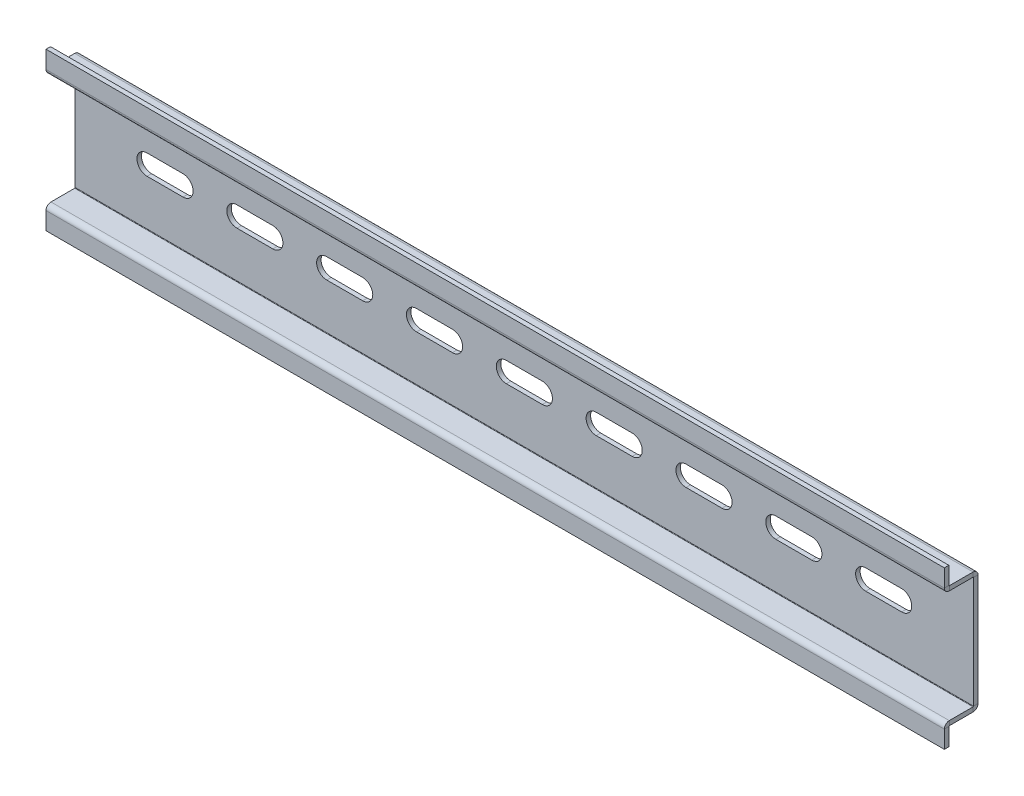
SolidWorks part; units mm, degrees
note: The reader was unsure of these and kept them because the rebuilt part matched: flange length of "边线-法兰1", "边线-法兰2".
material "冷轧钢板"
ref_plane "前视基准面" through (0, 0, 0) normal (0, 0, 1) x (1, 0, 0)
ref_plane "上视基准面" through (0, 0, 0) normal (0, 1, 0) x (1, 0, 0)
ref_plane "右视基准面" through (0, 0, 0) normal (1, 0, 0) x (0, 0, -1)
sketch "草图1" plane through (0, 0, 0) normal (0, 0, 1) x (1, 0, 0)
  line L1 (-100, 13.5) -> (100, 13.5)
  line L2 (-100, 13.5) -> (-100, -13.5)
  line L3 (-100, -13.5) -> (100, -13.5)
  line L4 (100, 13.5) -> (100, -13.5)
  line L5 (-100, 13.5) -> (100, -13.5) construction
  line L6 (-100, -13.5) -> (100, 13.5) construction
  point P0 (0, 0)
  dimension "D1" = 200
  dimension "D2" = 27
base flange "基体-法兰1" sketch "草图1" thickness 1 reverse thickness direction no parameters "D1"=0.1
edge flange "边线-法兰1" sketch "草图10" flange profiles "草图10", "草图11" flange angle 90 flange length 7.5 flange position material inside bend radius 0.1 thickness 1 parameters "D1"=1.5, "D6"=10, "D8"=1
sketch "草图10" plane through (0, 13.5, 0) normal (0, -1, 0) x (1, 0, 0)
  line L1 (100, 0) -> (-100, 0) construction
  line L2 (-100, 0) -> (-100, 6.5)
  line L3 (-100, 6.5) -> (100, 6.5)
  line L4 (100, 6.5) -> (100, 0)
  line L5 (100, 0) -> (-100, 0)
sketch "草图11" plane through (0, -13.5, 0) normal (0, 1, 0) x (-1, 0, 0)
  line L0 (100, 0) -> (-100, 0) construction
  line L1 (100, 0) -> (-100, 0)
  line L2 (100, 0) -> (100, 6.5)
  line L3 (100, 6.5) -> (-100, 6.5)
  line L4 (-100, 6.5) -> (-100, 0)
bend "边线折弯1" bend radius 0.1 bend angle 90 parameters "D5"=1
bend "边线折弯2" bend radius 0.1 bend angle 90 parameters "D5"=2
edge flange "边线-法兰2" sketch "草图16" flange profiles "草图16", "草图17" flange angle 90 flange length 5 flange position material inside bend radius 0.1 thickness 1 parameters "D1"=1.5, "D6"=10, "D8"=1
sketch "草图16" plane through (0, 13.5, 6.5) normal (0, 0, 1) x (1, 0, 0)
  line L2 (-100, 0) -> (-100, 4)
  line L3 (-100, 4) -> (100, 4)
  line L4 (100, 4) -> (100, 0)
  line L5 (100, 0) -> (-100, 0) construction
  line L6 (100, 0) -> (-100, 0)
sketch "草图17" plane through (0, -13.5, 6.5) normal (0, 0, 1) x (-1, 0, 0)
  line L0 (100, 0) -> (-100, 0) construction
  line L1 (100, 0) -> (-100, 0)
  line L2 (-100, 0) -> (-100, 4)
  line L3 (-100, 4) -> (100, 4)
  line L4 (100, 4) -> (100, 0)
bend "边线折弯3" bend radius 0.1 bend angle 90 parameters "D5"=3
bend "边线折弯4" bend radius 0.1 bend angle 90 parameters "D5"=4
sketch "草图18" plane through (0, 0, -1) normal (0, 0, -1) x (-1, 0, 0)
  line L0 (-4, 0) -> (4, 0) construction
  line L1 (-4, 2.25) -> (4, 2.25)
  line L2 (-4, -2.25) -> (4, -2.25)
  arc A0 (-4, 2.25) -> (-4, -2.25) centre (-4, 0) ccw
  arc A1 (4, -2.25) -> (4, 2.25) centre (4, 0) ccw
  point P3 (0, 0)
  dimension "D2" = 2.25
  dimension "D1" = 8
  dimension "D3" = 0
extrude "切除-拉伸1" cut sketch "草图18" against normal blind 10 normal cut yes
pattern_linear "阵列(线性)1" count 5 spacing 20 along (1, 0, 0) count 5 spacing 20 along (-1, 0, 0) of "切除-拉伸1"
sketch "折弯-线1" [suppressed] plane through (0, 0, 0) normal (0, 1, 0) x (1, 0, 0)
sketch "边界框1" [suppressed] plane through (0, 0, 0) normal (0, 1, 0) x (1, 0, 0)
sheet metal parameters "钣金9" thickness 1 parameters "D1"=0.1
flat pattern "平板型式9" [suppressed]
sketch "折弯-线2" plane through (0, 0, 0) normal (0, 1, 0) x (1, 0, 0)
sketch "边界框2" [suppressed] plane through (0, 0, 0) normal (0, 1, 0) x (1, 0, 0)
sheet metal parameters "钣金10" thickness 1 parameters "D1"=0.1
flat pattern "平板型式9" [suppressed]
sketch "折弯-线2" plane through (0, 0, 0) normal (0, 1, 0) x (1, 0, 0)
sketch "边界框2" [suppressed] plane through (0, 0, 0) normal (0, 1, 0) x (1, 0, 0)
bend of the flat pattern "展开-<边线折弯1>1"
bend of the flat pattern "展开-<边线折弯2>1"
sheet metal parameters "钣金11" thickness 1 parameters "D1"=0.1
flat pattern "平板型式9" [suppressed]
sketch "折弯-线2" plane through (0, 0, 0) normal (0, 1, 0) x (1, 0, 0)
sketch "边界框2" [suppressed] plane through (0, 0, 0) normal (0, 1, 0) x (1, 0, 0)
bend of the flat pattern "展开-<边线折弯1>1"
bend of the flat pattern "展开-<边线折弯2>1"
bend of the flat pattern "展开-<边线折弯3>1"
bend of the flat pattern "展开-<边线折弯4>1"
sheet metal parameters "钣金12" thickness 1 parameters "D1"=0.1
flat pattern "平板型式9" [suppressed]
sketch "折弯-线2" plane through (0, 0, 0) normal (0, 1, 0) x (1, 0, 0)
sketch "边界框2" [suppressed] plane through (0, 0, 0) normal (0, 1, 0) x (1, 0, 0)
bend of the flat pattern "展开-<边线折弯1>1"
bend of the flat pattern "展开-<边线折弯2>1"
bend of the flat pattern "展开-<边线折弯3>1"
bend of the flat pattern "展开-<边线折弯4>1"
sheet metal parameters "钣金13" thickness 1 parameters "D1"=0.1
flat pattern "平板型式9"
sketch "折弯-线2" plane through (0, 0, 0) normal (0, 0, 1) x (1, 0, 0)
  line L0 (-100, -18.45) -> (100, -18.45) construction
  line L1 (100, 18.45) -> (-100, 18.45) construction
  line L2 (-100, -12.65) -> (100, -12.65) construction
  line L3 (100, 12.65) -> (-100, 12.65) construction
  line L4 (-100, -18.45) -> (100, -18.45) construction
  line L5 (100, 18.45) -> (-100, 18.45) construction
  line L6 (-100, -12.65) -> (100, -12.65) construction
  line L7 (100, 12.65) -> (-100, 12.65) construction
sketch3d "边界框2" [suppressed]
  line L0 (-100, -22.6, 0) -> (100, -22.6, 0) construction
  line L1 (-100, 22.6, 0) -> (100, 22.6, 0) construction
  line L2 (-100, -22.6, 0) -> (-100, 22.6, 0) construction
  line L3 (100, -22.6, 0) -> (100, 22.6, 0) construction
bend of the flat pattern "展开-<边线折弯1>1"
bend of the flat pattern "展开-<边线折弯2>1"
bend of the flat pattern "展开-<边线折弯3>1"
bend of the flat pattern "展开-<边线折弯4>1"
